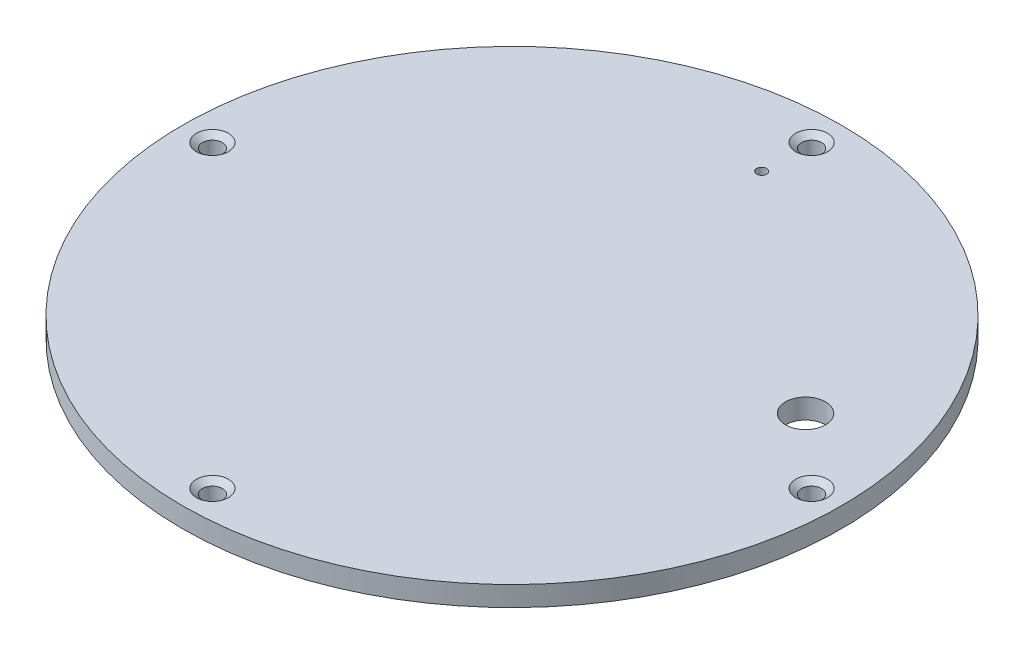
SolidWorks part; units mm, degrees
material "1060 Alloy"
ref_plane "Front Plane" through (0, 0, 0) normal (0, 0, 1) x (1, 0, 0)
ref_plane "Top Plane" through (0, 0, 0) normal (0, 1, 0) x (1, 0, 0)
ref_plane "Right Plane" through (0, 0, 0) normal (1, 0, 0) x (0, 0, -1)
sketch "Sketch1" plane through (0, 0, 0) normal (0, 1, 0) x (1, 0, 0)
  circle A0 centre (0, 0) radius 16.5
  dimension "D1" = 33
extrude "Boss-Extrude1" add sketch "Sketch1" along normal blind 1
sketch "Sketch6" plane through (0, 1, 0) normal (0, 1, 0) x (1, 0, 0)
  line L0 (0, 0) -> (17.9401, 4.807) construction
  line L1 (0, 0) -> (0, 12.5) construction
  circle A0 centre (0, 12.5) radius 0.25
  circle A1 centre (11.5911, 3.1058) radius 1
  dimension "D1" = 12.5
  dimension "D3" = 0.5
  dimension "D4" = 2
  dimension "D2" = 0
  dimension "D5" = 12
  dimension "D6" = 75
extrude "Cut-Extrude1" cut sketch "Sketch6" against normal through all both and the other way through all
hole_wizard "CSK for M2 Flat Head Machine Screw1" positions "Sketch13" profile "Sketch14" countersink size "M2" standard "ANSI Metric" end condition through all
sketch "Sketch13" plane through (0, 1, 0) normal (0, 1, 0) x (1, 0, 0)
  point P0 (0, 15)
  point P2 (-15, 0)
  point P4 (0, -15)
  point P6 (15, 0)
  dimension "D1" = 15
  dimension "D2" = 15
  dimension "D3" = 15
  dimension "D4" = 15
sketch "Sketch14" plane through (0, 1, -15) normal (1, 0, 0) x (0, 0, 1)
  line L0 (0, 0) -> (0, 1)
  line L1 (0, 1) -> (0.5, 1)
  line L2 (0.5, 1) -> (0.5, 0.2517)
  line L3 (0.5, 0.2517) -> (0.8, 0)
  line L5 (0.8, 0) -> (0, 0)
  line L6 (-0.5, 0.2517) -> (-0.8, 0) construction
  line L11 (0, -6.35) -> (0, 107.95) construction
  dimension "Thru Hole Dia." = 1
  dimension "Thru Hole Depth" = 1
  dimension "Near C'Sink Dia." = 1.6
  dimension "Near C'Sink Angle" = 100
